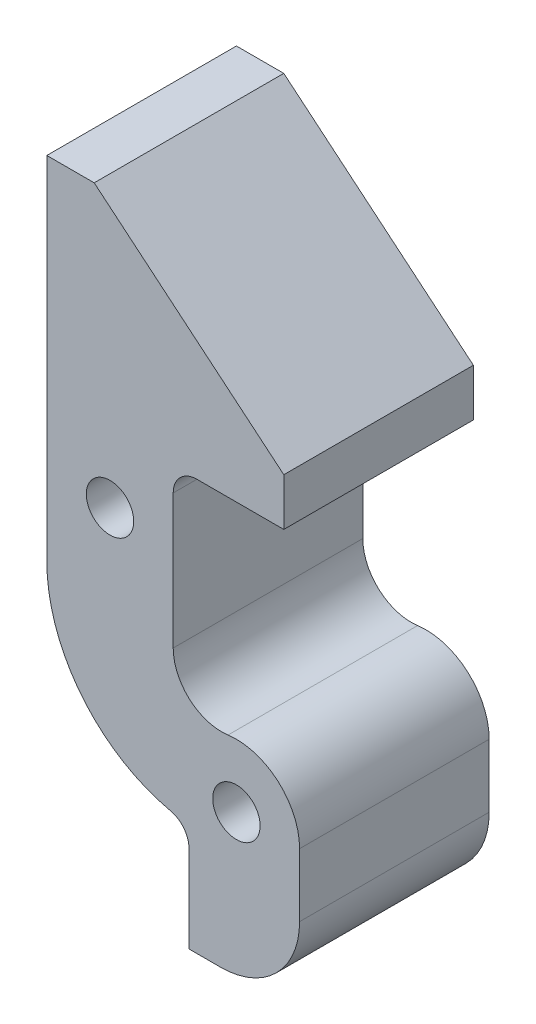
SolidWorks part; units mm, degrees
material "POM 乙缩醛共聚物"
ref_plane "前视基准面" through (0, 0, 0) normal (0, 0, 1) x (1, 0, 0)
ref_plane "上视基准面" through (0, 0, 0) normal (0, 1, 0) x (1, 0, 0)
ref_plane "右视基准面" through (0, 0, 0) normal (1, 0, 0) x (0, 0, -1)
sketch "草图1" plane through (0, 0, 0) normal (0, 0, 1) x (1, 0, 0)
  line L0 (-4, 7) -> (-4, 17)
  line L1 (-4, 17) -> (3, 17)
  line L3 (-9, 30) -> (-12, 30)
  line L4 (-12, 30) -> (-12, 7)
  line L5 (3, 17) -> (3, 20)
  line L6 (3, 20) -> (-9, 30)
  circle A3 centre (0, 0) radius 1.5
  arc A4 (0.531, -3.9646) -> (-0.531, 3.9646) centre (0, 0) ccw
  arc A5 (-4, 7) -> (-0.531, 3.9646) centre (-0.9375, 7) ccw
  arc A6 (-12, 7) -> (0.531, -3.9646) centre (-0.9375, 7) ccw
  circle A7 centre (-8, 12.6886) radius 1.5
  point P14 (-10.5, 30)
  dimension "D1" = 3
  dimension "D2" = 8
  dimension "D4" = 7
  dimension "D3" = 3
  dimension "D10" = 3
  dimension "D12" = 4
  dimension "D5" = 3
  dimension "D6" = 17
  dimension "D7" = 13
  dimension "D8" = 7
  dimension "D9" = 3
  dimension "D11" = 15
extrude "凸台-拉伸1" add sketch "草图1" along normal blind 12
fillet "圆角1" radius 1.5 1 edges at (-4, 17, 6)
sketch "草图2" plane through (0, 0, 0) normal (0, 0, -1) x (-1, 0, 0)
  line L0 (-4, 0) -> (-4, -9) construction
  line L1 (-4, -9) -> (0, -9) construction
  line L2 (0, -9) -> (0, -4.0227) construction
  line L3 (-4, 0) -> (-4, -9)
  line L4 (-4, -9) -> (0, -9)
  line L5 (0, -9) -> (0, -4.0227)
  line L6 (0, -4.0227) -> (-4, 0)
  arc A0 (0.531, 3.9646) -> (-0.531, -3.9646) centre (0, 0) ccw construction
  arc A1 (-0.531, -3.9646) -> (12, 7) centre (0.9375, 7) ccw construction
  dimension "D1" = 9
extrude "凸台-拉伸2" add sketch "草图2" against normal up to surface (12 mm away) up to face at (1.5, 0, 12)
sketch "草图3" plane through (0, 0, 0) normal (-1, 0, 0) x (0, 0, 1)
  line L1 (0, -9) -> (12, -9)
  line L2 (0, -9) -> (0, -2)
  line L3 (0, -2) -> (12, -2)
  line L4 (12, -9) -> (12, -2)
  dimension "D1" = 7
extrude "凸台-拉伸4" add sketch "草图3" along normal blind 3
fillet "圆角3" radius 5 1 edges at (4, -9, 6)
sketch "草图4" plane through (0, 0, 0) normal (0, 0, -1) x (-1, 0, 0)
  line L0 (3, -3.8685) -> (3, -9) construction
  circle A0 centre (4.5, -3.4732) radius 1.5
  arc A1 (3, -3.8685) -> (12, 7) centre (0.9375, 7) ccw construction
  dimension "D1" = 3
extrude "切除-拉伸1" cut sketch "草图4" against normal through all
fillet "圆角4" radius 10 1 edges at (-5.8841, -2.895, 6)
fillet "圆角5" radius 10 1 edges at (-3.0504, -3.8588, 6)
